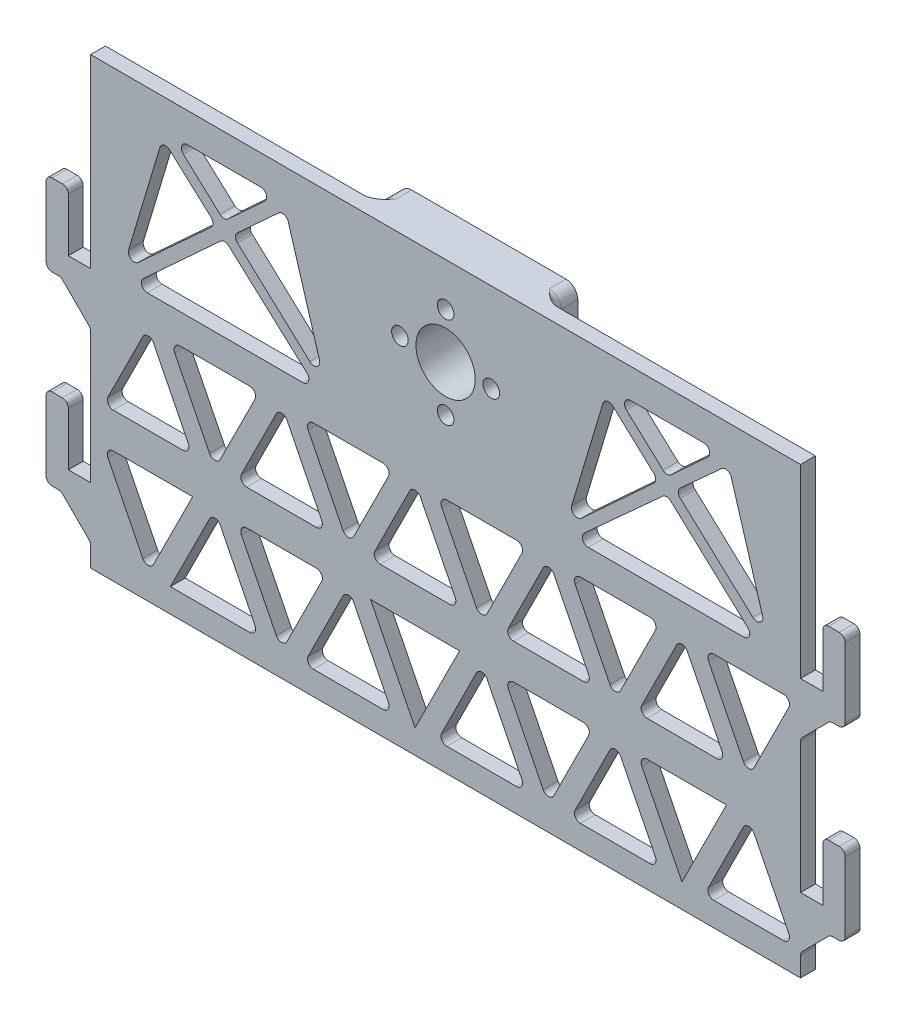
SolidWorks part; units mm, degrees
ref_plane "Front" through (0, 0, 0) normal (0, 0, 1) x (1, 0, 0)
ref_plane "Top" through (0, 0, 0) normal (0, 1, 0) x (1, 0, 0)
ref_plane "Right" through (0, 0, 0) normal (1, 0, 0) x (0, 0, -1)
sketch "Sketch1" plane through (0, 0, 0) normal (0, 0, 1) x (1, 0, 0)
  line L1 (0, 0) -> (-38.1, 0)
  line L2 (0, 0) -> (0, -38.1)
  line L3 (0, -38.1) -> (-38.1, -38.1)
  line L4 (-38.1, 0) -> (-38.1, -38.1)
  dimension "D1" = 38.1
  dimension "D2" = 38.1
extrude "Boss-Extrude1" add sketch "Sketch1" along normal blind 9.2583
sketch "Sketch2" plane through (0, 0, 9.2583) normal (0, 0, 1) x (1, 0, 0)
  line L0 (0, 0) -> (-38.1, 0) construction
  line L1 (0, -38.1) -> (0, 0) construction
  circle A0 centre (-19.05, -19.05) radius 6.35
  dimension "D1" = 12.7
  dimension "D2" = 19.05
  dimension "D3" = 19.05
extrude "Cut-Extrude1" cut sketch "Sketch2" against normal blind 10.8458
sketch "Sketch3" plane through (0, 0, 9.2583) normal (0, 0, 1) x (1, 0, 0)
  circle A0 centre (-19.05, -9.271) radius 1.778
  circle A1 centre (-19.05, -19.05) radius 6.35 construction
  dimension "D1" = 3.556
  dimension "D2" = 9.779
extrude "Cut-Extrude2" cut sketch "Sketch3" against normal blind 10.8458
pattern_circular "CirPattern1" count 4 over 360 about axis through (-19.05, -19.05, 9.2583) along (0, 0, 1) of "Cut-Extrude2"
sketch "Sketch4" plane through (0, 0, 9.2583) normal (0, 0, 1) x (1, 0, 0)
  line L1 (-38.1, 0) -> (-95.058, 0)
  line L2 (-38.1, 0) -> (-38.1, -95.2246)
  line L3 (-38.1, -95.2246) -> (-95.058, -95.2246)
  line L4 (-95.058, 0) -> (-95.058, -95.2246)
  line L5 (0, 0) -> (56.958, 0)
  line L6 (0, 0) -> (0, -95.2246)
  line L7 (0, -95.2246) -> (56.958, -95.2246)
  line L8 (56.958, 0) -> (56.958, -95.2246)
  dimension "D1" = 56.958
  dimension "D2" = 56.958
  dimension "D3" = 95.2246
  dimension "D4" = 95.2246
extrude "Boss-Extrude2" add sketch "Sketch4" against normal blind 3.175
sketch "Sketch5" plane through (0, 0, 6.0833) normal (0, 0, -1) x (-1, 0, 0)
  line L1 (0, -38.1) -> (38.1, -38.1)
  line L2 (0, -38.1) -> (0, -95.2246)
  line L3 (0, -95.2246) -> (38.1, -95.2246)
  line L4 (38.1, -38.1) -> (38.1, -95.2246)
extrude "Boss-Extrude3" add sketch "Sketch5" against normal blind 3.175
fillet "Fillet1" radius 2.54 4 edges at (-38.1, 0, 3.0416) (-38.1, -38.1, 3.0416) (0, -38.1, 3.0416) (0, 0, 3.0416)
fillet "Fillet2" radius 2.54 7 edges at (-0.7439, -0.7439, 6.0833) (-37.3561, -0.7439, 6.0833) (-38.1, -19.05, 6.0833) (-37.3561, -37.3561, 6.0833) (-19.05, -38.1, 6.0833) (-0.7439, -37.3561, 6.0833) (0, -19.05, 6.0833)
sketch "Sketch6" plane through (0, 0, 6.0833) normal (0, 0, -1) x (-1, 0, 0)
  line L0 (-56.958, -95.2246) -> (-56.958, 0) construction
  line L1 (-56.958, -39.6875) -> (-61.7205, -39.6875)
  line L2 (-56.958, -39.6875) -> (-56.958, -44.45)
  line L3 (-56.958, -44.45) -> (-66.483, -44.45)
  line L5 (-66.483, -26.9875) -> (-66.483, -44.45)
  line L8 (-66.483, -26.9875) -> (-61.7205, -26.9875)
  line L9 (-61.7205, -39.6875) -> (-61.7205, -26.9875)
  line L10 (-56.958, 0) -> (-1.8594, 0) construction
  point P3 (-59.3392, -39.6875)
  dimension "D1" = 4.7625
  dimension "D2" = 4.7625
  dimension "D3" = 4.7625
  dimension "D4" = 12.7
  dimension "D5" = 44.45
extrude "Boss-Extrude4" add sketch "Sketch6" against normal blind 3.175
sketch "Sketch7" plane through (0, 0, 6.0833) normal (0, 0, -1) x (-1, 0, 0)
  line L0 (-56.958, -84.1375) -> (-66.483, -84.1375)
  line L1 (-56.958, -95.2246) -> (-56.958, -44.45) construction
  line L2 (-66.483, -66.675) -> (-66.483, -84.1375)
  line L3 (-61.7205, -79.375) -> (-56.958, -79.375)
  line L4 (-61.7205, -79.375) -> (-61.7205, -66.675)
  line L5 (-61.7205, -66.675) -> (-66.483, -66.675)
  line L6 (-56.958, -79.375) -> (-56.958, -84.1375)
  line L7 (-66.483, -44.45) -> (-56.958, -44.45) construction
  dimension "D1" = 4.7625
  dimension "D2" = 4.7625
  dimension "D3" = 12.7
  dimension "D4" = 4.7625
  dimension "D5" = 22.225
extrude "Boss-Extrude5" add sketch "Sketch7" against normal blind 3.175
chamfer "Chamfer1" distance 6.35 angle 45 2 edges at (56.958, -84.1375, 7.6708) (56.958, -44.45, 7.6708)
fillet "Fillet3" radius 1.27 10 edges at (66.483, -26.9875, 7.6708) (61.7205, -26.9875, 7.6708) (66.483, -44.45, 7.6708) (63.308, -44.45, 7.6708) (56.958, -50.8, 7.6708) (66.483, -66.675, 7.6708) (66.483, -84.1375, 7.6708) (61.7205, -66.675, 7.6708) (56.958, -90.4875, 7.6708) (63.308, -84.1375, 7.6708)
ref_plane "Plane1" through (-19.05, 0, 0) normal (1, 0, 0) x (0, 0, -1)
mirror "Mirror2" about plane through (-19.05, 0, 0) normal (1, 0, 0) of "Boss-Extrude5", "Boss-Extrude4"
chamfer "Chamfer2" distance 6.35 angle 45 2 edges at (-95.058, -44.45, 7.6708) (-95.058, -84.1375, 7.6708)
fillet "Fillet4" radius 1.27 10 edges at (-95.058, -50.8, 7.6708) (-101.408, -44.45, 7.6708) (-104.583, -44.45, 7.6708) (-104.583, -26.9875, 7.6708) (-99.8205, -26.9875, 7.6708) (-99.8205, -66.675, 7.6708) (-104.583, -66.675, 7.6708) (-104.583, -84.1375, 7.6708) (-101.408, -84.1375, 7.6708) (-95.058, -90.4875, 7.6708)
sketch "Sketch8" plane through (0, 0, 6.0833) normal (0, 0, -1) x (-1, 0, 0)
  line L0 (-50.608, -38.1) -> (-6.158, -38.1)
  line L1 (-6.158, -38.1) -> (-15.683, -6.35)
  line L2 (-15.683, -6.35) -> (-41.083, -6.35)
  line L3 (-41.083, -6.35) -> (-50.608, -38.1)
  line L4 (-56.958, -39.6875) -> (-56.958, 0) construction
  line L5 (-56.958, 0) -> (-1.8594, 0) construction
  dimension "D1" = 44.45
  dimension "D2" = 6.35
  dimension "D3" = 6.35
  dimension "D4" = 31.75
  dimension "D5" = 25.4
  dimension "D6" = 9.525
extrude "Cut-Extrude3" cut sketch "Sketch8" against normal blind 4.7625
mirror "Mirror3" about plane through (-19.05, 0, 0) normal (1, 0, 0) of "Cut-Extrude3"
sketch "Sketch9" plane through (0, 0, 6.0833) normal (0, 0, -1) x (-1, 0, 0)
  line L0 (-41.5391, -7.8705) -> (-8.19, -38.1)
  line L1 (-41.083, -6.35) -> (-50.608, -38.1) construction
  line L2 (-50.608, -38.1) -> (-6.158, -38.1) construction
  line L3 (-8.19, -38.1) -> (-6.158, -38.1)
  line L4 (-6.158, -38.1) -> (-6.6141, -36.5795)
  line L5 (-6.158, -38.1) -> (-15.683, -6.35) construction
  line L6 (-6.6141, -36.5795) -> (-39.4955, -6.35)
  line L7 (-15.683, -6.35) -> (-41.083, -6.35) construction
  line L8 (-39.4955, -6.35) -> (-41.083, -6.35)
  line L9 (-41.083, -6.35) -> (-41.5391, -7.8705)
  dimension "D1" = 2.032
  dimension "D2" = 1.5875
  dimension "D3" = 1.5875
  dimension "D4" = 1.5875
extrude "Boss-Extrude6" add sketch "Sketch9" against normal blind 3.175
sketch "Sketch10" plane through (0, 0, 6.0833) normal (0, 0, -1) x (-1, 0, 0)
  line L0 (-50.608, -38.1) -> (-48.068, -38.1)
  line L1 (-50.608, -38.1) -> (-8.19, -38.1) construction
  line L2 (-48.068, -38.1) -> (-15.2268, -7.8705)
  line L3 (-6.6141, -36.5795) -> (-15.683, -6.35) construction
  line L4 (-15.2268, -7.8705) -> (-15.683, -6.35)
  line L5 (-15.683, -6.35) -> (-17.2705, -6.35)
  line L6 (-15.683, -6.35) -> (-39.4955, -6.35) construction
  line L7 (-17.2705, -6.35) -> (-50.1518, -36.5795)
  line L8 (-41.5391, -7.8705) -> (-50.608, -38.1) construction
  line L9 (-50.1518, -36.5795) -> (-50.608, -38.1)
  dimension "D1" = 2.54
  dimension "D2" = 1.5875
  dimension "D3" = 1.5875
  dimension "D4" = 1.5875
extrude "Boss-Extrude7" add sketch "Sketch10" against normal blind 3.175
mirror "Mirror4" about plane through (-19.05, 0, 0) normal (1, 0, 0) of "Boss-Extrude7", "Boss-Extrude6"
fillet "Fillet5" radius 1.27 12 edges at (15.2268, -7.8705, 7.6708) (17.2705, -6.35, 7.6708) (39.4955, -6.35, 7.6708) (41.5391, -7.8705, 7.6708) (50.1518, -36.5795, 7.6708) (26.5273, -18.2723, 7.6708) (30.1519, -18.1925, 7.6708) (28.383, -16.5663, 7.6708) (6.6141, -36.5795, 7.6708) (8.19, -38.1, 7.6708) (48.068, -38.1, 7.6708) (28.282, -19.8875, 7.6708)
fillet "Fillet6" radius 1.27 12 edges at (-79.6391, -7.8705, 7.6708) (-88.2518, -36.5795, 7.6708) (-86.168, -38.1, 7.6708) (-68.2519, -18.1925, 7.6708) (-66.382, -19.8875, 7.6708) (-77.5955, -6.35, 7.6708) (-55.3705, -6.35, 7.6708) (-66.483, -16.5663, 7.6708) (-53.3268, -7.8705, 7.6708) (-64.6273, -18.2723, 7.6708) (-44.7141, -36.5795, 7.6708) (-46.29, -38.1, 7.6708)
sketch "Sketch11" plane through (0, 0, 6.0833) normal (0, 0, -1) x (-1, 0, 0)
  line L0 (-55.3705, -44.45) -> (-36.3205, -44.45)
  line L1 (-36.3205, -44.45) -> (-45.8455, -63.5)
  line L2 (-45.8455, -63.5) -> (-55.3705, -44.45)
  line L3 (-44.813, -38.1) -> (-11.482, -38.1) construction
  line L4 (-56.958, -79.375) -> (-56.958, -51.3261) construction
  line L5 (-41.083, -63.5) -> (-31.558, -44.45)
  line L6 (-31.558, -44.45) -> (-22.033, -63.5)
  line L7 (-22.033, -63.5) -> (-41.083, -63.5)
  dimension "D1" = 6.35
  dimension "D2" = 19.05
  dimension "D3" = 19.05
  dimension "D4" = 9.525
  dimension "D5" = 1.5875
  dimension "D6" = 19.05
  dimension "D7" = 19.05
  dimension "D8" = 9.525
  dimension "D9" = 4.7625
extrude "Cut-Extrude4" cut sketch "Sketch11" against normal blind 3.175
pattern_linear "LPattern1" count 5 spacing 28.575 along (-1, 0, 0) of "Cut-Extrude4"
ref_plane "Plane2" through (0, -67.2846, 0) normal (0, -1, 0) x (-1, 0, 0)
mirror "Mirror5" about plane through (0, -67.2846, 0) normal (0, -1, 0) of "LPattern1"
fillet "Fillet7" radius 1.27 53 edges at (-92.267, -71.0692, 7.6708) (-68.4545, -71.0692, 7.6708) (-82.742, -44.45, 7.6708) (-77.9795, -44.45, 7.6708) (-92.267, -63.5, 7.6708) (-58.9295, -44.45, 7.6708) (-58.9295, -90.1192, 7.6708) (-73.217, -63.5, 7.6708) (-68.4545, -63.5, 7.6708) (-82.742, -90.1192, 7.6708) (-54.167, -90.1192, 7.6708) (-44.642, -71.0692, 7.6708) (-44.642, -63.5, 7.6708) (-54.167, -44.45, 7.6708) (-63.692, -63.5, 7.6708) (-63.692, -71.0692, 7.6708) (-49.4045, -44.45, 7.6708) (-49.4045, -90.1192, 7.6708) (-30.3545, -90.1192, 7.6708) (-39.8795, -71.0692, 7.6708) (-30.3545, -44.45, 7.6708) (-39.8795, -63.5, 7.6708) (-16.067, -63.5, 7.6708) (-35.117, -63.5, 7.6708) (-25.592, -44.45, 7.6708) (-11.3045, -63.5, 7.6708) (-20.8295, -44.45, 7.6708) (-11.3045, -71.0692, 7.6708) (-1.7795, -90.1192, 7.6708) (-20.8295, -90.1192, 7.6708) (2.983, -90.1192, 7.6708) (-6.542, -71.0692, 7.6708) (2.983, -44.45, 7.6708) (-6.542, -63.5, 7.6708) (12.508, -63.5, 7.6708) (12.508, -71.0692, 7.6708) (17.2705, -71.0692, 7.6708) (26.7955, -90.1192, 7.6708) (55.3705, -90.1192, 7.6708) (7.7455, -90.1192, 7.6708) (36.3205, -90.1192, 7.6708) (22.033, -63.5, 7.6708) (17.2705, -63.5, 7.6708) (7.7455, -44.45, 7.6708) (22.033, -71.0692, 7.6708) (45.8455, -71.0692, 7.6708) (31.558, -44.45, 7.6708) (41.083, -63.5, 7.6708) (45.8455, -63.5, 7.6708) (36.3205, -44.45, 7.6708) (-1.7795, -44.45, 7.6708) (26.7955, -44.45, 7.6708) (55.3705, -44.45, 7.6708)
